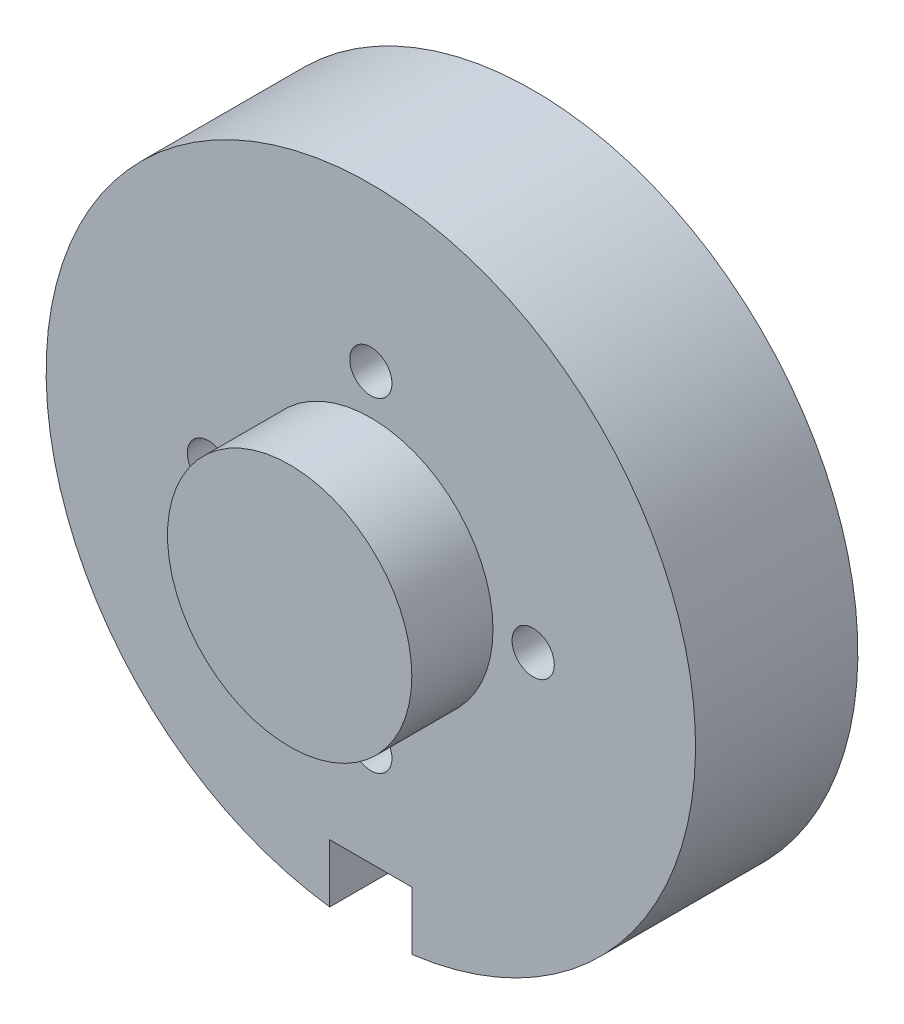
SolidWorks part; units mm, degrees
ref_plane "Front Plane" through (0, 0, 0) normal (0, 0, 1) x (1, 0, 0)
ref_plane "Top Plane" through (0, 0, 0) normal (0, 1, 0) x (1, 0, 0)
ref_plane "Right Plane" through (0, 0, 0) normal (1, 0, 0) x (0, 0, -1)
sketch "Sketch1" plane through (0, 0, 0) normal (0, 0, 1) x (1, 0, 0)
  line L1 (-6.4262, -41.275) -> (6.4262, -41.275)
  line L2 (-6.4262, -41.275) -> (-6.4262, -50.3919)
  line L4 (6.4262, -41.275) -> (6.4262, -50.3919)
  arc A0 (6.4262, -50.3919) -> (-6.4262, -50.3919) centre (0, 0) ccw
  circle A1 centre (0, 0) radius 25.4 construction
  circle A2 centre (0, 25.4) radius 3.302
  circle A3 centre (25.4, 0) radius 3.302
  circle A4 centre (0, -25.4) radius 3.302
  circle A5 centre (-25.4, 0) radius 3.302
  circle A6 centre (0, 0) radius 19.1135
  point P6 (0, -41.275)
  dimension "D1" = 50.8
  dimension "D2" = 25.4
  dimension "D3" = 6.604
  dimension "D7" = 38.227
  dimension "D5" = 12.8524
  dimension "D6" = 41.275
  dimension "D4" = 4
extrude "Boss-Extrude1" add sketch "Sketch1" against normal blind 25.4 contours A6 | L4 A0 L2 L1 A6 A5 A4 A3 A2 region at (-7.8602, -45.8335, 0) region at (0, 0, 0)
extrude "Boss-Extrude2" add sketch "Sketch1<4>" along normal blind 12.7 contours A6 region at (0, 0, 0)
sketch "Sketch1<4>" plane through (0, 0, 0) normal (0, 0, 1) x (1, 0, 0) same geometry as "Sketch1"
